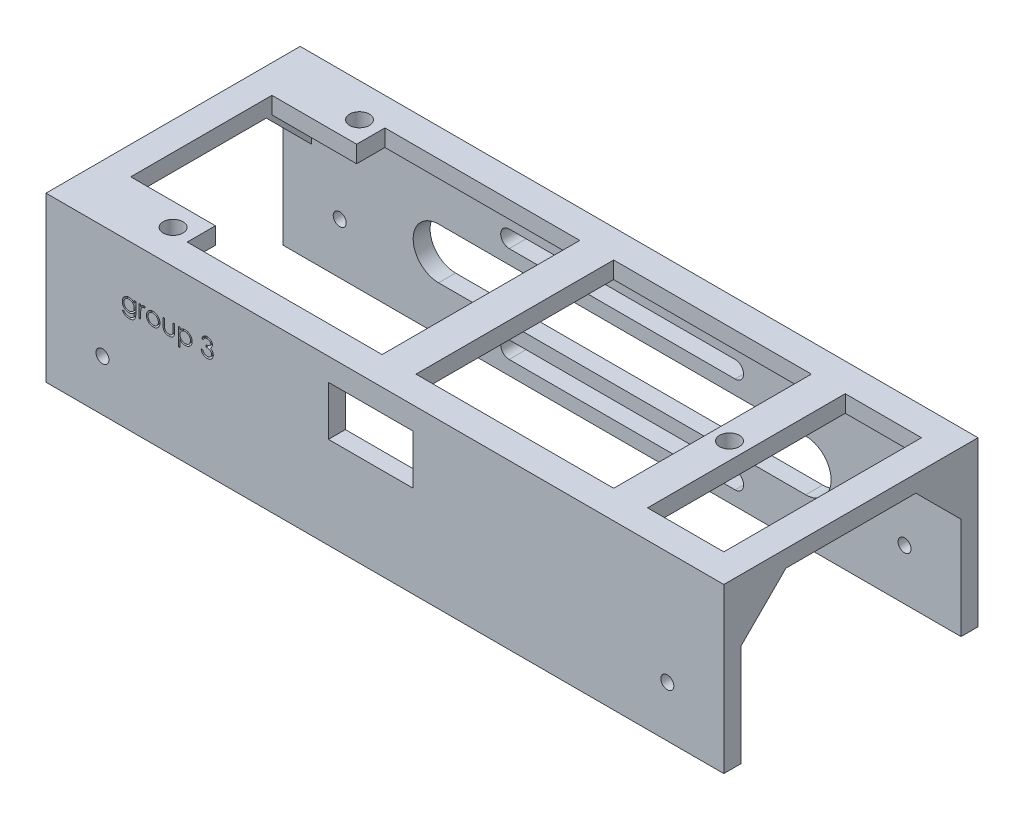
SolidWorks part; units mm, degrees
other "Markup1"
sketch "Sketch23" plane through (120, 29, 45) normal (0.0467, 0.9512, 0.3049) x (0.9885, 0, -0.1514)
sketch "Sketch24" plane through (120, 29, 45) normal (0.0467, 0.9512, 0.3049) x (0.9885, 0, -0.1514)
sketch "Sketch25" plane through (120, 29, 45) normal (0.0467, 0.9512, 0.3049) x (0.9885, 0, -0.1514)
sketch "Sketch26" plane through (120, 29, 45) normal (0.0467, 0.9512, 0.3049) x (0.9885, 0, -0.1514)
sketch "Sketch27" plane through (120, 29, 45) normal (0.0467, 0.9512, 0.3049) x (0.9885, 0, -0.1514)
sketch "Sketch28" plane through (120, 29, 45) normal (0.0467, 0.9512, 0.3049) x (0.9885, 0, -0.1514)
ref_plane "Front Plane" through (0, 0, 0) normal (0, 0, 1) x (1, 0, 0)
ref_plane "Top Plane" through (0, 0, 0) normal (0, 1, 0) x (1, 0, 0)
ref_plane "Right Plane" through (0, 0, 0) normal (1, 0, 0) x (0, 0, -1)
sketch "Sketch1" plane through (0, 0, 0) normal (0, 0, 1) x (1, 0, 0)
  line L9 (21.172, -17.9478) -> (91.172, -17.9478)
  line L10 (21.172, -17.9478) -> (21.172, -40.3878)
  line L11 (4, -8) -> (200.227, -8) construction
  line L12 (4, -8) -> (-67.5185, -8) construction
  line L13 (21.172, -40.3878) -> (91.172, -40.3878)
  line L14 (91.172, -17.9478) -> (91.172, -40.3878)
  line L15 (0, 0) -> (120, 0)
  line L16 (0, 0) -> (0, 29)
  line L17 (0, 29) -> (120, 29)
  line L18 (120, 0) -> (120, 29)
  circle A0 centre (4, 7) radius 1.15
  circle A1 centre (4, 7) radius 15 construction
  circle A3 centre (77.172, -29.1678) radius 3.6067
  circle A4 centre (116, 7) radius 15 construction
  circle A5 centre (116, 7) radius 1.15
  point P19 (21.172, -29.1678)
  dimension "D4" = 30
  dimension "D2" = 14
  dimension "D7" = 30
  dimension "D11" = 4
  dimension "D13" = 2.3
  dimension "D14" = 2.3
  dimension "D3" = 70
  dimension "D5" = 22.44
  dimension "D6" = 120
  dimension "D8" = 29
  dimension "D9" = 4
  dimension "D10" = 7
  dimension "D12" = 7
extrude "Boss-Extrude5" add sketch "Sketch1" along normal blind 45 contours L16 L15 L18 L17
shell "Shell9" thickness 3 removed face at (120, 14.5, 22.5) removed face at (60, 0, 22.5) removed face at (0, 14.5, 22.5)
sketch "Sketch3" plane through (0, 0, 0) normal (0, 0, -1) x (-1, 0, 0)
  line L0 (0, 0) -> (-120, 0) construction
  line L1 (-120, 0) -> (-120, 29) construction
  line L2 (0, 0) -> (0, 29) construction
  circle A0 centre (-10, 9) radius 1.15
  circle A1 centre (-110, 9) radius 1.15
  dimension "D1" = 2.3
  dimension "D2" = 2.3
  dimension "D3" = 9
  dimension "D4" = 10
  dimension "D5" = 9
  dimension "D6" = 10
extrude "Cut-Extrude2" cut sketch "Sketch3" against normal blind 79
sketch "Sketch6" plane through (0, 0, 0) normal (0, 0, -1) x (-1, 0, 0)
  line L0 (-80, 21) -> (-40, 21) construction
  line L1 (-80, 22.5) -> (-40, 22.5)
  line L2 (-80, 19.5) -> (-40, 19.5)
  line L7 (-60, 29) -> (-60, 0) construction
  line L8 (-92.5, 12.5) -> (-27.5, 12.5) construction
  line L9 (-92.5, 17) -> (-27.5, 17)
  line L10 (-92.5, 8) -> (-27.5, 8)
  line L11 (-27.5, 12.5) -> (-14.9525, 12.5) construction
  line L12 (-80, 4) -> (-40, 4) construction
  line L13 (-80, 2.5) -> (-40, 2.5)
  line L14 (-80, 5.5) -> (-40, 5.5)
  line L15 (0, 0) -> (-120, 0) construction
  line L26 (0, 29) -> (-120, 29) construction
  arc A4 (-92.5, 17) -> (-92.5, 8) centre (-92.5, 12.5) ccw
  arc A5 (-80, 22.5) -> (-80, 19.5) centre (-80, 21) ccw
  arc A6 (-40, 19.5) -> (-40, 22.5) centre (-40, 21) ccw
  arc A7 (-27.5, 8) -> (-27.5, 17) centre (-27.5, 12.5) ccw
  arc A8 (-80, 2.5) -> (-80, 5.5) centre (-80, 4) cw
  arc A9 (-40, 5.5) -> (-40, 2.5) centre (-40, 4) cw
  point P11 (-60, 21)
  point P19 (-60, 12.5)
  point P31 (-60, 4)
  dimension "D3" = 20
  dimension "D8" = 1.5
  dimension "D13" = 4.5
  dimension "D2" = 8.5
  dimension "D16" = 65
  dimension "D19" = 16.5
extrude "Cut-Extrude8" cut sketch "Sketch6" against normal blind 23 contours L10 A7 L9 | L2 A6 L1 A5 | L13 A9 L14 A8 region at (60, 21, 0) region at (60, 12.5, 0)
sketch "Sketch7" plane through (0, 0, 45) normal (0, 0, 1) x (1, 0, 0)
  line L1 (50, 25) -> (65, 25)
  line L2 (50, 25) -> (50, 16.25)
  line L3 (50, 16.25) -> (65, 16.25)
  line L4 (65, 25) -> (65, 16.25)
  line L5 (0, 0) -> (120, 0) construction
  line L7 (0, 0) -> (0, 29) construction
  dimension "D1" = 50
  dimension "D2" = 15
  dimension "D3" = 8.75
  dimension "D4" = 25
extrude "Cut-Extrude9" cut sketch "Sketch7" against normal blind 20
sketch "Sketch13" plane through (0, 29, 0) normal (0, 1, 0) x (1, 0, 0)
  line L1 (0, 0) -> (120, 0) construction
  line L4 (5, -5) -> (115, -5)
  line L5 (5, -5) -> (5, -40)
  line L6 (5, -40) -> (115, -40)
  line L8 (0, -45) -> (0, 0) construction
  line L16 (115, -5) -> (115, -40)
  line L17 (120, -45) -> (120, 0) construction
  dimension "D1" = 5
  dimension "D2" = 5
  dimension "D5" = 5
  dimension "D6" = 35
extrude "Cut-Extrude14" cut sketch "Sketch13" against normal blind 10
sketch "Sketch17" plane through (0, 29, 0) normal (0, 1, 0) x (1, 0, 0)
  line L0 (0, -22.5) -> (120, -22.5) construction
  line L1 (5, -5) -> (20, -5)
  line L2 (5, -5) -> (5, -10)
  line L3 (5, -10) -> (20, -10)
  line L4 (20, -5) -> (20, -10)
  line L5 (5, -40) -> (20, -40)
  line L6 (5, -40) -> (5, -35)
  line L7 (5, -35) -> (20, -35)
  line L8 (20, -40) -> (20, -35)
  line L17 (0, -45) -> (0, 0) construction
  line L18 (120, -45) -> (120, 0) construction
  line L25 (115, -5) -> (5, -5) construction
  line L26 (95.5, -5) -> (101.5, -5)
  line L27 (95.5, -5) -> (95.5, -40)
  line L28 (95.5, -40) -> (101.5, -40)
  line L29 (101.5, -5) -> (101.5, -40)
  line L30 (5, -40) -> (115, -40) construction
  line L32 (54.5, -5) -> (60.5, -5)
  line L33 (54.5, -5) -> (54.5, -40)
  line L34 (54.5, -40) -> (60.5, -40)
  line L35 (60.5, -5) -> (60.5, -40)
  circle A0 centre (16.5, -39) radius 1.75
  circle A1 centre (16.5, -6) radius 1.75
  circle A2 centre (98.5, -22.5) radius 1.75
  point P41 (98.5, -5)
  line M10 (5, -40) -> (5, -5)
  line M11 (5, -5) -> (115, -5)
  line M13 (115, -40) -> (5, -40)
  dimension "D3" = 3.5
  dimension "D6" = 3.5
  dimension "D11" = 33
  dimension "D12" = 16.5
  dimension "D13" = 3.5
  dimension "D1" = 5
  dimension "D2" = 15
  dimension "D4" = 5
  dimension "D5" = 15
  dimension "D7" = 6
  dimension "D8" = 18.5
  dimension "D9" = 6
  dimension "D10" = 35
extrude "Boss-Extrude6" add sketch "Sketch17" against normal blind 3 contours A1 L3 L4 M11 M10 | L1 A1 | A0 L8 L7 M13 M10 | L5 A0 | L33 L32 L35 L34 | L27 L26 L29 L28 region at (12.0151, 29, 7.6523) region at (16.5, 29, 6.2435) region at (12.0151, 29, 37.3477) region at (16.5, 29, 38.7565)
extrude "Cut-Extrude16" cut sketch "Sketch17<4>" against normal blind 10 contours A2 L0 | L0 A2 | L1 A1 | L1 A1 | L5 A0 | L5 A0 | A2 region at (98.5, 29, 21.7573) region at (98.5, 29, 23.2427) region at (16.5, 29, 4.6937) region at (16.5, 29, 6.2435) region at (16.5, 29, 38.7565) region at (16.5, 29, 40.3063)
sketch "Sketch17<4>" plane through (0, 29, 0) normal (0, 1, 0) x (1, 0, 0) same geometry as "Sketch17"
sketch "Sketch20" plane through (0, 0, 45) normal (0, 0, 1) x (1, 0, 0)
  line L0 (13.2558, 18.0126) -> (38.9246, 18.0126) construction
  text T0 "group 3"
extrude "Cut-Extrude15" cut sketch "Sketch20" against normal blind 1.5
sketch "Sketch21" plane through (0, 0, 0) normal (-1, 0, 0) x (0, 0, 1)
  line L0 (3, 26) -> (3, 18)
  line L1 (3, 0) -> (3, 26) construction
  line L2 (3, 18) -> (11, 26)
  line L3 (42, 26) -> (3, 26) construction
  line L4 (11, 26) -> (3, 26)
  line L5 (42, 26) -> (34, 26)
  line L6 (34, 26) -> (42, 18)
  line L7 (42, 0) -> (42, 26) construction
  line L8 (42, 18) -> (42, 26)
  dimension "D1" = 8
  dimension "D2" = 8
  dimension "D3" = 8
  dimension "D4" = 8
extrude "Boss-Extrude7" add sketch "Sketch21" against normal blind 5
sketch "Sketch22" plane through (120, 0, 0) normal (1, 0, 0) x (0, 0, -1)
  line L0 (-42, 26) -> (-42, 18)
  line L1 (-42, 18) -> (-34, 26)
  line L2 (-34, 26) -> (-42, 26)
  line L3 (-11, 26) -> (-3, 26)
  line L4 (-3, 26) -> (-3, 18)
  line L5 (-3, 18) -> (-11, 26)
extrude "Boss-Extrude8" add sketch "Sketch22" against normal blind 5
equation "\"slot­_width\"=25.09"
